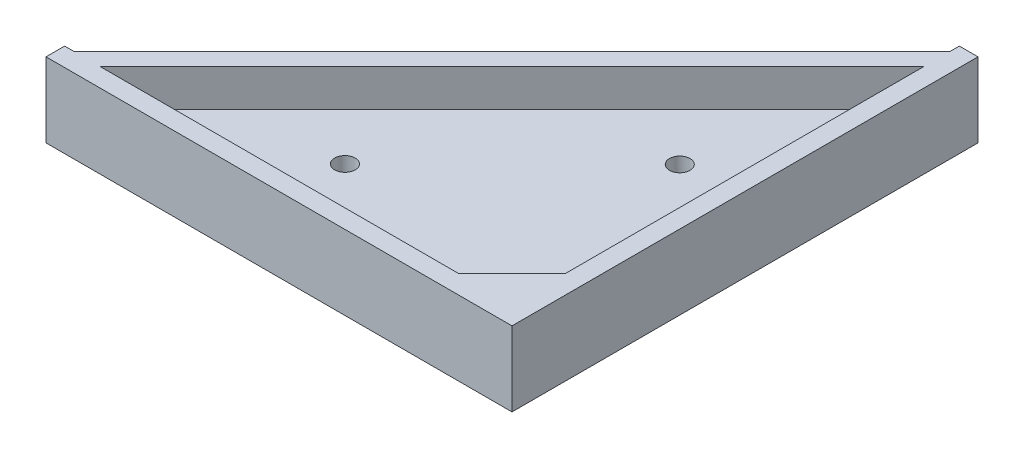
SolidWorks part; units mm, degrees
ref_plane "Front Plane" through (0, 0, 0) normal (0, 0, 1) x (1, 0, 0)
ref_plane "Top Plane" through (0, 0, 0) normal (0, 1, 0) x (1, 0, 0)
ref_plane "Right Plane" through (0, 0, 0) normal (1, 0, 0) x (0, 0, -1)
sketch "Sketch1" plane through (0, 0, 0) normal (0, 1, 0) x (1, 0, 0)
  line L0 (-79.375, 0) -> (0, 0)
  line L1 (0, 0) -> (0, 79.375)
  line L2 (0, 79.375) -> (-3.175, 79.375)
  line L3 (-3.175, 79.375) -> (-3.175, 77.7875)
  line L4 (-3.175, 77.7875) -> (-77.7875, 3.175)
  line L5 (-77.7875, 3.175) -> (-79.375, 3.175)
  line L6 (-79.375, 3.175) -> (-79.375, 0)
  point P2 (47.0322, -59.0093)
  point P8 (0, 0)
  point P9 (-0.6815, -0.6646)
  point P10 (0, 0)
  dimension "D1" = 76.2
  dimension "D2" = 79.375
  dimension "D3" = 3.175
  dimension "D4" = 1.5875
extrude "Boss-Extrude1" add sketch "Sketch1" along normal blind 12.7
sketch "Sketch2" plane through (0, 12.7, 0) normal (0, 1, 0) x (1, 0, 0)
  line L0 (-73.2974, 3.175) -> (-12.2411, 3.175)
  line L1 (-3.175, 12.2411) -> (-3.175, 73.2974)
  line L2 (-3.175, 73.2974) -> (-73.2974, 3.175)
  line L3 (-12.2411, 3.175) -> (-3.175, 12.2411)
  line L5 (-79.375, 0) -> (0, 0) construction
  line L6 (0, 0) -> (0, 79.375) construction
  line L7 (-3.175, 77.7875) -> (-77.7875, 3.175) construction
  point P1 (-12.2411, 4.0072)
  point P5 (-4.6038, 68.4466)
  point P12 (-128.8267, 29.8272)
  dimension "D2" = 3.175
  dimension "D3" = 3.175
  dimension "D4" = 3.175
extrude "Cut-Extrude1" cut sketch "Sketch2" against normal blind 6.35
chamfer "Chamfer1" distance 6.35 angle 45 1 edges at (-7.708, 6.35, -7.708)
sketch "Sketch3" plane through (0, 6.35, 0) normal (0, 1, 0) x (1, 0, 0)
  line L0 (-79.375, 0) -> (0, 0) construction
  line L1 (0, 0) -> (0, 79.375) construction
  circle A0 centre (-44.4608, 16.002) radius 1.75
  circle A1 centre (-15.875, 44.45) radius 1.75
  dimension "D1" = 3.5
  dimension "D2" = 3.5
  dimension "D3" = 16.002
  dimension "D4" = 44.4608
  dimension "D5" = 15.875
  dimension "D6" = 44.45
extrude "Cut-Extrude2" cut sketch "Sketch3" against normal blind 6.35
